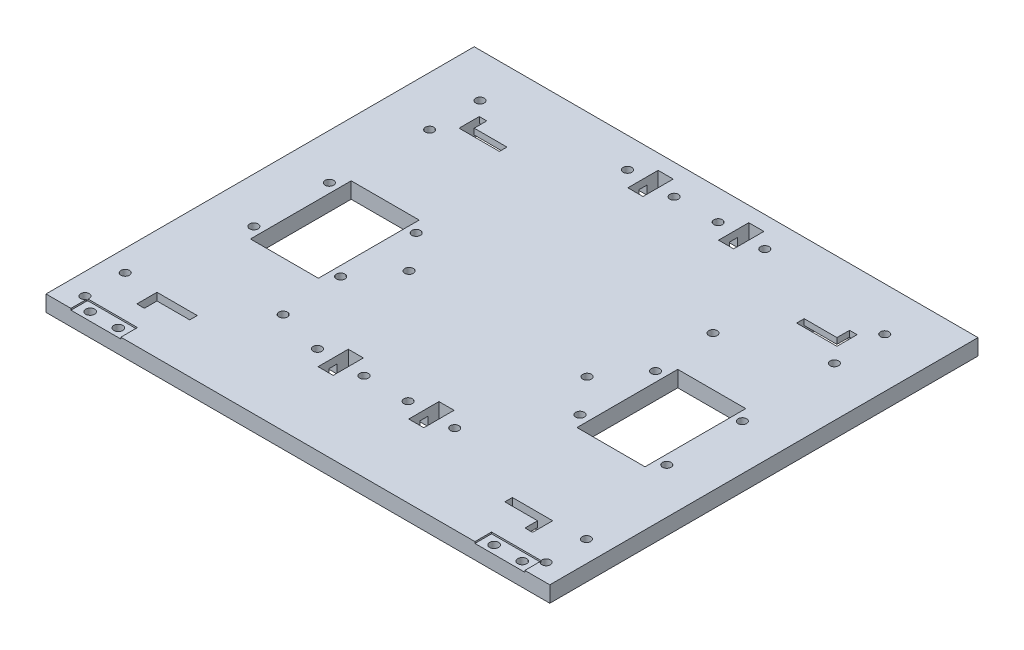
SolidWorks part; units mm, degrees
material "1023 Carbon Steel Sheet (SS)"
ref_plane "Front Plane" through (0, 0, 0) normal (0, 0, 1) x (1, 0, 0)
ref_plane "Top Plane" through (0, 0, 0) normal (0, 1, 0) x (1, 0, 0)
ref_plane "Right Plane" through (0, 0, 0) normal (1, 0, 0) x (0, 0, -1)
sketch "Sketch1" plane through (0, 0, 0) normal (0, 1, 0) x (1, 0, 0)
  line L1 (-100, -85) -> (100, -85)
  line L2 (-100, -85) -> (-100, 85)
  line L3 (-100, 85) -> (100, 85)
  line L4 (100, -85) -> (100, 85)
  line L5 (-100, -85) -> (100, 85) construction
  line L6 (-100, 85) -> (100, -85) construction
  point P0 (0, 0)
  dimension "D1" = 200
  dimension "D2" = 170
extrude "1/4\" Steel Plate" add sketch "Sketch1" along normal blind 6.35
ref_plane "Midplane" through (0, 0, 0) normal (-1, 0, 0) x (0, 0, 1)
sketch "Sketch2" plane through (0, 6.35, 0) normal (0, 1, 0) x (1, 0, 0)
  line L0 (-100, -85) -> (100, -85) construction
  line L1 (-90.094, -85) -> (-70.282, -85)
  line L2 (-90.094, -85) -> (-90.094, -78.396)
  line L3 (-90.094, -78.396) -> (-70.282, -78.396)
  line L4 (-70.282, -85) -> (-70.282, -78.396)
  line L5 (-100, 85) -> (-100, -85) construction
  dimension "D1" = 9.906
  dimension "D2" = 6.604
  dimension "D3" = 19.812
extrude "BladeHingeCut" cut sketch "Sketch2" against normal blind 0.635
hole_wizard "BladeHingeHole" positions "3DSketch2" profile "Sketch4" hole size "#8" standard "ANSI Inch" end condition through all
sketch3d "3DSketch2"
  line L0 (-90.094, 5.715, 85) -> (-70.282, 5.715, 85) construction
  line L10 (-80.188, 5.715, 78.396) -> (-80.188, 5.715, 85) construction
  line L11 (-70.282, 5.715, 78.396) -> (-90.094, 5.715, 78.396) construction
  point P0 (-74.6, 5.715, 81.698)
  point P2 (-85.776, 5.715, 81.698)
  dimension "D1" = 3.302
  dimension "D2" = 3.302
  dimension "D3" = 11.176
  dimension "D4" = 5.588
sketch "Sketch4" plane through (-74.6, 5.715, 81.698) normal (1, 0, 0) x (0, 0, 1)
  line L0 (0, 0) -> (0, 5.715)
  line L1 (0, 5.715) -> (1.778, 5.715)
  line L2 (1.778, 5.715) -> (1.778, 0)
  line L5 (1.778, 0) -> (0, 0)
  line L11 (0, -6.35) -> (0, 107.95) construction
  dimension "Thru Hole Dia." = 3.556
  dimension "Thru Hole Depth" = 5.715
sketch "Sketch5" plane through (0, 0, 0) normal (0, -1, 0) x (1, 0, 0)
  line L1 (-88.301, 79.173) -> (-83.251, 79.173)
  line L2 (-88.301, 79.173) -> (-88.301, 84.223)
  line L3 (-88.301, 84.223) -> (-83.251, 84.223)
  line L4 (-83.251, 79.173) -> (-83.251, 84.223)
  line L5 (-88.301, 79.173) -> (-83.251, 84.223) construction
  line L6 (-88.301, 84.223) -> (-83.251, 79.173) construction
  line L7 (-72.075, 79.173) -> (-77.125, 79.173)
  line L8 (-72.075, 79.173) -> (-72.075, 84.223)
  line L9 (-72.075, 84.223) -> (-77.125, 84.223)
  line L10 (-77.125, 79.173) -> (-77.125, 84.223)
  line L11 (-72.075, 79.173) -> (-77.125, 84.223) construction
  line L12 (-72.075, 84.223) -> (-77.125, 79.173) construction
  point P0 (-85.776, 81.698)
  point P6 (-74.6, 81.698)
  dimension "D1" = 5.05
  dimension "D2" = 5.05
  dimension "D3" = 5.05
  dimension "D4" = 5.05
extrude "BladeNutCut" cut sketch "Sketch5" against normal blind 2
mirror "BladeHingeMirror" about plane through (0, 0, 0) normal (-1, 0, 0) of "BladeNutCut", "BladeHingeHole", "BladeHingeCut"
sketch "Sketch6" plane through (0, 0, 0) normal (0, -1, 0) x (-1, 0, 0)
  line L0 (77.3259, -27.4233) -> (77.3259, 16.3767) construction
  line L1 (78.3259, 14.4767) -> (51.3259, 14.4767)
  line L2 (78.3259, 14.4767) -> (78.3259, -25.5233)
  line L3 (78.3259, -25.5233) -> (51.3259, -25.5233)
  line L4 (51.3259, 14.4767) -> (51.3259, -25.5233)
  line L5 (57.3259, 16.3767) -> (57.3259, -27.4233) construction
  point P6 (78.3259, -5.5233)
  dimension "D1" = 1
  dimension "D2" = 20
  dimension "D3" = 6
  dimension "D4" = 20
extrude "Cut-Extrude1" cut sketch "Sketch6" against normal up to surface (6.35 mm away) up to face at (0, 6.35, 54.4653)
sketch "Sketch7" plane through (0, 0, 0) normal (0, -1, 0) x (-1, 0, 0)
  line L0 (51.3259, -25.5233) -> (78.3259, -25.5233) construction
  line L1 (79.3259, -30.5233) -> (49.3259, -30.5233)
  line L2 (79.3259, -30.5233) -> (79.3259, -40.5233)
  line L3 (79.3259, -40.5233) -> (49.3259, -40.5233)
  line L4 (49.3259, -30.5233) -> (49.3259, -40.5233)
  line L5 (80.3259, 19.4767) -> (50.3259, 19.4767)
  line L6 (80.3259, 19.4767) -> (80.3259, 29.4767)
  line L7 (80.3259, 29.4767) -> (50.3259, 29.4767)
  line L8 (50.3259, 19.4767) -> (50.3259, 29.4767)
  line L9 (29.3259, -25.5233) -> (19.3259, -25.5233)
  line L10 (29.3259, -25.5233) -> (29.3259, 14.4767)
  line L11 (29.3259, 14.4767) -> (19.3259, 14.4767)
  line L12 (19.3259, -25.5233) -> (19.3259, 14.4767)
  line L17 (78.3259, -25.5233) -> (78.3259, 14.4767) construction
  line L18 (78.3259, 14.4767) -> (51.3259, 14.4767) construction
  line L19 (51.3259, 14.4767) -> (51.3259, -25.5233) construction
  line L29 (46.3259, -80.5233) -> (36.3259, -80.5233)
  line L30 (46.3259, -80.5233) -> (46.3259, -50.5233)
  line L31 (46.3259, -50.5233) -> (36.3259, -50.5233)
  line L32 (36.3259, -80.5233) -> (36.3259, -50.5233)
  line L33 (20, -70.5233) -> (-20, -70.5233)
  line L34 (20, -70.5233) -> (20, -60.5233)
  line L35 (20, -60.5233) -> (-20, -60.5233)
  line L36 (-20, -70.5233) -> (-20, -60.5233)
  line L37 (-100, 85) -> (100, 85) construction
  line L38 (36.3259, 39.4767) -> (46.3259, 39.4767)
  line L39 (36.3259, 39.4767) -> (36.3259, 69.4767)
  line L40 (36.3259, 69.4767) -> (46.3259, 69.4767)
  line L41 (46.3259, 39.4767) -> (46.3259, 69.4767)
  line L42 (20, 49.4767) -> (-20, 49.4767)
  line L43 (20, 49.4767) -> (20, 59.4767)
  line L44 (20, 59.4767) -> (-20, 59.4767)
  line L45 (-20, 49.4767) -> (-20, 59.4767)
  point P18 (0, 49.4767)
  point P55 (20, 54.4767)
  point P56 (36.3259, 54.4767)
  point P57 (20, -65.5233)
  point P58 (36.3259, -65.5233)
  point P60 (0, 85)
  dimension "D1" = 5
  dimension "D2" = 30
  dimension "D3" = 10
  dimension "D4" = 1
  dimension "D5" = 5
  dimension "D6" = 1
  dimension "D7" = 10
  dimension "D8" = 30
  dimension "D9" = 40
  dimension "D10" = 10
  dimension "D11" = 22
  dimension "D14" = 10
  dimension "D17" = 5
  dimension "D18" = 40
  dimension "D19" = 10
  dimension "D20" = 30
  dimension "D21" = 25
  dimension "D22" = 10
  dimension "D23" = 30
  dimension "D24" = 25
  dimension "D25" = 10
  dimension "D26" = 40
other "AlignGroup1"
extrude "Cut-Extrude2" cut sketch "Sketch7" against normal blind 5 contours L30 L29 L32 L31 | L34 L33 L36 L35 | L10 L9 L12 L11 | L2 L1 L4 L3 | L6 L5 L8 L7 | L39 L38 L41 L40 | L43 L42 L45 L44
sketch "Sketch8" plane through (0, 6.35, 0) normal (0, 1, 0) x (1, 0, 0)
  line L0 (-83.5459, -55) -> (-83.5459, -85) construction
  line L1 (-78.5459, -62.396) -> (-62.5459, -62.396)
  line L2 (-78.5459, -62.396) -> (-78.5459, -73.396)
  line L3 (-78.5459, -73.396) -> (-62.5459, -73.396)
  line L4 (-62.5459, -62.396) -> (-62.5459, -73.396)
  line L5 (-70.282, -78.396) -> (-90.094, -78.396) construction
  dimension "D1" = 11
  dimension "D2" = 16
  dimension "D3" = 5
  dimension "D4" = 5
extrude "Cut-Extrude3" cut sketch "Sketch8" along normal blind 4 from surface starting at face at (0, 0, -54.4767)
sketch "Sketch9" plane through (0, 4, 0) normal (0, -1, 0) x (1, 0, 0)
  line L0 (-78.5459, 62.396) -> (-62.5459, 62.396)
  line L9 (-78.5459, 62.396) -> (-78.5459, 70.396)
  line L10 (-78.5459, 73.396) -> (-78.5459, 62.396) construction
  line L11 (-78.5459, 70.396) -> (-75.5459, 70.396)
  line L12 (-75.5459, 70.396) -> (-75.5459, 65.396)
  line L13 (-75.5459, 65.396) -> (-62.5459, 65.396)
  line L14 (-62.5459, 62.396) -> (-62.5459, 73.396) construction
  line L15 (-62.5459, 65.396) -> (-62.5459, 62.396)
  dimension "D1" = 8
  dimension "D2" = 3
  dimension "D3" = 3
extrude "Cut-Extrude4" cut sketch "Sketch9" against normal up to surface (2.35 mm away) contours L13 L15 L0 L9 L11 L12 up to face at (-64.8259, 6.35, 5.5233)
sketch "Sketch10" plane through (0, 0, 0) normal (0, -1, 0) x (-1, 0, 0)
  line L1 (75, 65) -> (59, 65)
  line L2 (75, 65) -> (75, 54)
  line L3 (75, 54) -> (59, 54)
  line L4 (59, 65) -> (59, 54)
  line L6 (100, 85) -> (100, -85) construction
  line L7 (-100, 85) -> (100, 85) construction
  dimension "D1" = 11
  dimension "D2" = 16
  dimension "D3" = 25
  dimension "D4" = 20
extrude "Cut-Extrude5" cut sketch "Sketch10" against normal blind 4
sketch "Sketch11" plane through (0, 4, 0) normal (0, -1, 0) x (1, 0, 0)
  line L0 (-59, -54) -> (-75, -54)
  line L1 (-75, -54) -> (-75, -62)
  line L2 (-75, -54) -> (-75, -65) construction
  line L3 (-75, -62) -> (-72, -62)
  line L4 (-72, -62) -> (-72, -57)
  line L5 (-72, -57) -> (-59, -57)
  line L6 (-59, -65) -> (-59, -54) construction
  line L7 (-59, -57) -> (-59, -54)
  dimension "D1" = 3
  dimension "D2" = 3
  dimension "D3" = 8
extrude "Cut-Extrude6" cut sketch "Sketch11" against normal up to next
mirror "Mirror2" about plane through (0, 0, 0) normal (-1, 0, 0) of "Cut-Extrude6", "Cut-Extrude5", "Cut-Extrude4", "Cut-Extrude3", "Cut-Extrude2", "Cut-Extrude1"
hole_wizard "CSK for M3 Flat Head Machine Screw1" positions "Sketch12" profile "Sketch13" countersink size "M3" standard "ANSI Metric"
sketch "Sketch12" plane through (0, 0, 0) normal (0, -1, 0) x (-1, 0, 0)
  point P0 (-91.5503, -78)
  point P2 (-91.5503, -62)
  point P4 (-80.3371, 47.6378)
  point P7 (-80.3371, 67.6378)
  point P10 (-35.8509, -6.0466)
  point P13 (-45.8509, 33.9534)
  point P16 (35.8509, -5)
  point P19 (45.8509, -45)
  point P22 (91.5459, -62)
  point P25 (91.5459, -78)
  point P28 (80.3371, 47.6378)
  point P31 (80.3371, 67.6378)
  point P39 (-81.9659, -20.5233)
  point P42 (-81.9659, 9.4767)
  point P45 (-47.5109, -20.5233)
  point P48 (-47.5109, 9.4767)
  point P51 (47.5109, -20.5233)
  point P54 (81.9659, -20.5233)
  point P57 (81.9659, 9.4767)
  point P60 (47.5109, 9.4767)
sketch "Sketch13" plane through (91.5503, 0, 78) normal (1, 0, 0) x (0, 0, -1)
  line L0 (0, 0) -> (0, 14)
  line L1 (0, 14) -> (1.7, 14)
  line L2 (1.7, 14) -> (1.7, 1.45)
  line L3 (1.7, 1.45) -> (3.15, 0)
  line L5 (3.15, 0) -> (0, 0)
  line L6 (-1.7, 1.45) -> (-3.15, 0) construction
  line L10 (0, 14) -> (-1.7, 14) construction
  line L11 (0, -6.35) -> (0, 107.95) construction
  dimension "Hole Dia." = 3.4
  dimension "Hole Depth" = 14
  dimension "Near C'Sink Dia." = 6.3
  dimension "Near C'Sink Angle" = 90
  dimension "Drill Angle" = 180
sketch "Sketch14" plane through (0, 0, 0) normal (0, -1, 0) x (1, 0, 0)
  line L0 (0, -7.6262) -> (0, -14.6112) construction
  line L1 (21, 56) -> (15, 56)
  line L2 (21, 56) -> (21, 44)
  line L3 (21, 44) -> (15, 44)
  line L4 (15, 56) -> (15, 44)
  line L6 (-100, 85) -> (100, 85) construction
  point P6 (15, 50)
  dimension "D1" = 6
  dimension "D2" = 12
  dimension "D3" = 15
  dimension "D4" = 35
extrude "Cut-Extrude7" cut sketch "Sketch14" against normal blind 10
sketch "Sketch15" plane through (0, 0, 0) normal (0, -1, 0) x (1, 0, 0)
  line L1 (10.75, 48.4) -> (25.25, 48.4)
  line L2 (10.75, 48.4) -> (10.75, 51.6)
  line L3 (10.75, 51.6) -> (25.25, 51.6)
  line L4 (25.25, 48.4) -> (25.25, 51.6)
  line L5 (15, 56) -> (15, 44) construction
  line L6 (15, 44) -> (21, 44) construction
  point P6 (18, 44)
  point P9 (15, 50)
  point P10 (10.75, 50)
  point P11 (18, 48.4)
  dimension "D2" = 14.5
  dimension "D3" = 3.2
extrude "Cut-Extrude8" cut sketch "Sketch15" against normal blind 3.5
sketch "Sketch16" plane through (0, 0, 0) normal (0, -1, 0) x (1, 0, 0)
  line L0 (15, 44) -> (21, 44) construction
  line L1 (15, -79) -> (21, -79)
  line L2 (15, -79) -> (15, -67)
  line L3 (15, -67) -> (21, -67)
  line L4 (21, -79) -> (21, -67)
  line L5 (100, -85) -> (-100, -85) construction
  point P6 (18, 44)
  point P7 (18, -67)
  point P8 (15, -73)
  dimension "D1" = 12
  dimension "D2" = 6
  dimension "D3" = 12
extrude "Cut-Extrude9" cut sketch "Sketch16" against normal through all
sketch "Sketch17" plane through (0, 0, 0) normal (0, -1, 0) x (1, 0, 0)
  line L1 (10.75, -74.6) -> (25.25, -74.6)
  line L2 (10.75, -74.6) -> (10.75, -71.4)
  line L3 (10.75, -71.4) -> (25.25, -71.4)
  line L4 (25.25, -74.6) -> (25.25, -71.4)
  line L8 (21, -67) -> (15, -67) construction
  line L9 (15, -67) -> (15, -79) construction
  point P6 (15, -73)
  point P7 (10.75, -73)
  point P14 (18, -67)
  point P15 (18, -71.4)
  dimension "D1" = 14.5
  dimension "D2" = 3.2
extrude "Cut-Extrude10" cut sketch "Sketch17" against normal blind 3.5
hole_wizard "CSK for M3 Flat Head Machine Screw2" positions "Sketch18" profile "Sketch19" countersink size "M3" standard "ANSI Metric"
sketch "Sketch18" plane through (0, 0, 0) normal (0, -1, 0) x (-1, 0, 0)
  line L0 (-36.6491, -50) -> (24.8009, -50) construction
  line L2 (-21, 74.6) -> (-25.25, 74.6) construction
  line L4 (-10.75, 74.6) -> (-15, 74.6) construction
  line L5 (-25.25, 74.6) -> (-25.25, 71.4) construction
  line L6 (-10.75, 71.4) -> (-10.75, 74.6) construction
  point P0 (-8.75, -50)
  point P4 (-27.25, -50)
  point P6 (-8.75, 73.1)
  point P8 (-27.25, 73.1)
  point P14 (0, 0)
  point P21 (0, 0)
  point P22 (0, 0)
  dimension "D1" = 1.5
  dimension "D2" = 1.5
  dimension "D3" = 2
  dimension "D4" = 2
sketch "Sketch19" plane through (8.75, 0, 50) normal (1, 0, 0) x (0, 0, -1)
  line L0 (0, 0) -> (0, 11.0215)
  line L1 (0, 11.0215) -> (1.7, 10)
  line L2 (1.7, 10) -> (1.7, 1.45)
  line L3 (1.7, 1.45) -> (3.15, 0)
  line L5 (3.15, 0) -> (0, 0)
  line L6 (-1.7, 1.45) -> (-3.15, 0) construction
  line L10 (0, 11.0215) -> (-1.7, 10) construction
  line L11 (0, -6.35) -> (0, 107.95) construction
  dimension "Hole Dia." = 3.4
  dimension "Hole Depth" = 10
  dimension "Near C'Sink Dia." = 6.3
  dimension "Near C'Sink Angle" = 90
  dimension "Drill Angle" = 118
mirror "Mirror3" about plane through (0, 0, 0) normal (-1, 0, 0) of "Cut-Extrude7", "Cut-Extrude8", "Cut-Extrude9", "Cut-Extrude10", "CSK for M3 Flat Head Machine Screw2"
